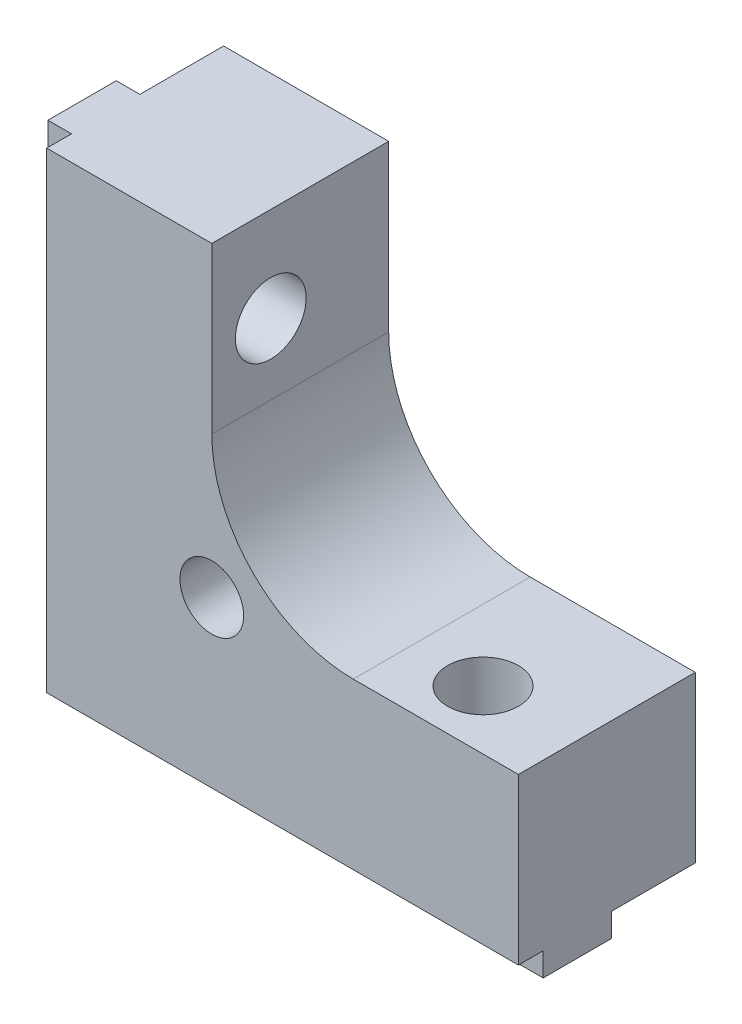
SolidWorks part; units mm, degrees
ref_plane "Front Plane" through (0, 0, 0) normal (0, 0, 1) x (1, 0, 0)
ref_plane "Top Plane" through (0, 0, 0) normal (0, 1, 0) x (1, 0, 0)
ref_plane "Right Plane" through (0, 0, 0) normal (1, 0, 0) x (0, 0, -1)
sketch "Esquisse1" plane through (0, 0, 0) normal (0, 0, 1) x (1, 0, 0)
  line L0 (0, 0) -> (20, 0)
  line L1 (20, 0) -> (20, 7)
  line L2 (20, 7) -> (13, 7)
  line L4 (7, 13) -> (7, 20)
  line L5 (7, 20) -> (0, 20)
  line L6 (0, 20) -> (0, 0)
  arc A0 (13, 7) -> (7, 13) centre (13, 13) cw
  dimension "D1" = 6
  dimension "D2" = 20
  dimension "D3" = 7
  dimension "D4" = 7
  dimension "D5" = 7
extrude "Main" add sketch "Esquisse1" along normal blind 10
sketch "Esquisse4" plane through (0, 0, 0) normal (-1, 0, 0) x (0, 0, 1)
  line L0 (10, 20) -> (0, 20) construction
  line L1 (3.55, 20) -> (6.45, 20)
  line L2 (3.55, 20) -> (3.55, 0)
  line L3 (3.55, 0) -> (6.45, 0)
  line L4 (6.45, 20) -> (6.45, 0)
  line L5 (10, 0) -> (0, 0) construction
  point P8 (5, 20)
  point P9 (5, 20)
  dimension "D1" = 2.9
extrude "MakerBeamFixVertical" add sketch "Esquisse4" along normal blind 1
sketch "Esquisse2" plane through (0, 0, 0) normal (-1, 0, 0) x (0, 0, 1)
  line L0 (10, 20) -> (6.45, 20) construction
  line L1 (10, 20) -> (0, 20) construction
  circle A0 centre (5, 16) radius 1.5
  point P9 (5, 20)
  dimension "D1" = 3
  dimension "D2" = 4
extrude "MakerBeamVerticalHole" cut sketch "Esquisse2" against normal through all both and the other way through all
sketch "Esquisse5" plane through (0, 0, 0) normal (0, -1, 0) x (-1, 0, 0)
  line L0 (-20, -10) -> (-20, 0) construction
  line L1 (0, -3.55) -> (-20, -3.55)
  line L2 (0, -3.55) -> (0, -6.45)
  line L3 (0, -6.45) -> (-20, -6.45)
  line L4 (-20, -3.55) -> (-20, -6.45)
  line L5 (1, -6.45) -> (0, -6.45) construction
extrude "MakerBeamFixHorizontal" add sketch "Esquisse5" along normal blind 1
sketch "Esquisse3" plane through (0, 0, 0) normal (0, -1, 0) x (1, 0, 0)
  line L0 (20, 10) -> (20, 6.45) construction
  line L1 (20, 10) -> (20, 0) construction
  circle A0 centre (16, 5) radius 1.5
  point P2 (20, 5)
  point P3 (0, 0)
  dimension "D1" = 3
  dimension "D2" = 4
extrude "MakerBeamHorizontalHole" cut sketch "Esquisse3" against normal through all both and the other way through all
sketch "Sketch1" plane through (0, 0, 10) normal (0, 0, 1) x (1, 0, 0)
  line L0 (0, 0) -> (20, 0) construction
  line L3 (0, 20) -> (0, 0) construction
  circle A0 centre (7, 7) radius 1.35
  dimension "D1" = 2.7
  dimension "D2" = 7
  dimension "D3" = 7
extrude "WindowFixHole" cut sketch "Sketch1" against normal through all
sketch "Sketch2" plane through (0, 0, 0) normal (-1, 0, 0) x (0, 0, 1)
  line L0 (10, 20) -> (6.45, 20) construction
  line L1 (7.5, 20) -> (10, 20)
  line L2 (7.5, 20) -> (7.5, 0)
  line L3 (7.5, 0) -> (10, 0)
  line L4 (10, 20) -> (10, 0)
  dimension "D1" = 2.5
extrude "Window" cut sketch "Sketch2" against normal through all
